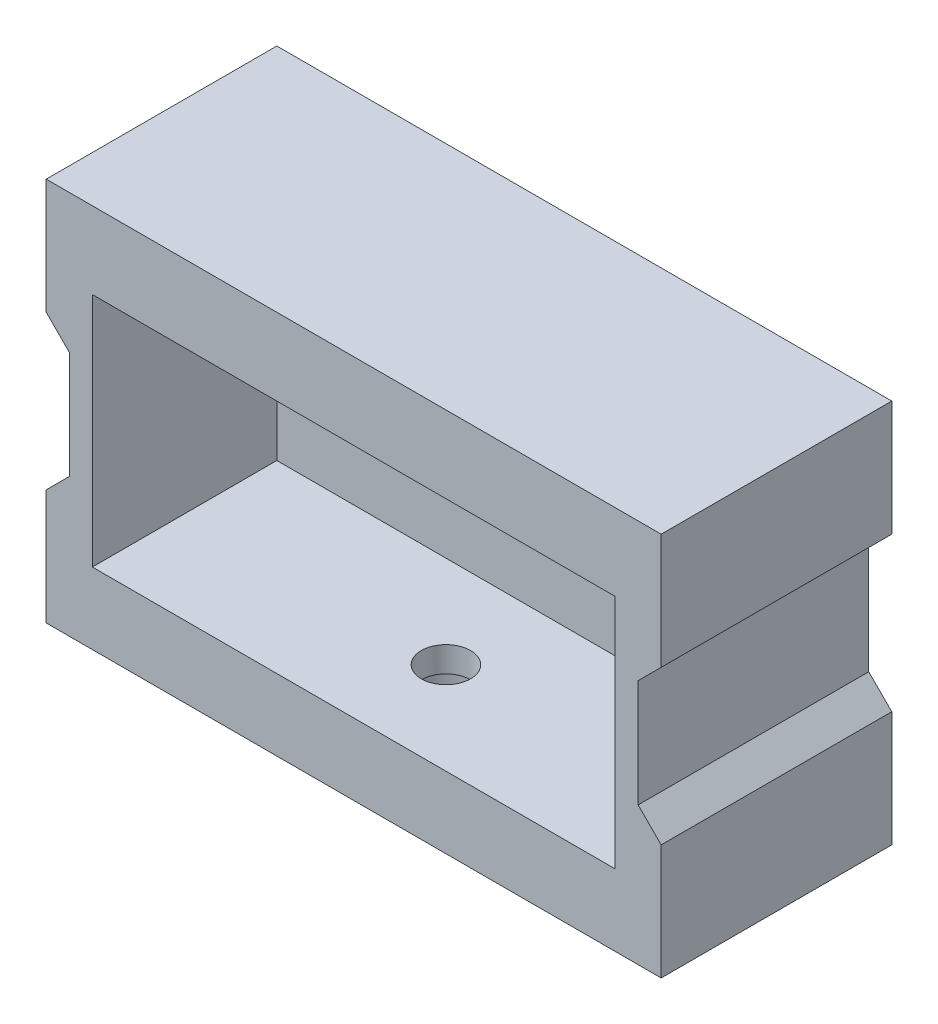
SolidWorks part; units mm, degrees
ref_plane "Płaszczyzna przednia" through (0, 0, 0) normal (0, 0, 1) x (1, 0, 0)
ref_plane "Płaszczyzna górna" through (0, 0, 0) normal (0, 1, 0) x (1, 0, 0)
ref_plane "Płaszczyzna prawa" through (0, 0, 0) normal (1, 0, 0) x (0, 0, -1)
sketch "Sketch1" plane through (0, 0, 0) normal (0, 0, 1) x (1, 0, 0)
  line L1 (-40, -25) -> (40, -25)
  line L2 (-40, -25) -> (-40, 25)
  line L3 (-40, 25) -> (40, 25)
  line L4 (40, -25) -> (40, 25)
  line L5 (-40, -25) -> (40, 25) construction
  line L6 (-40, 25) -> (40, -25) construction
  point P0 (0, 0)
  dimension "D1" = 80
  dimension "D2" = 50
extrude "Boss-Extrude1" add sketch "Sketch1" along normal blind 30
sketch "Sketch2" plane through (0, 0, 0) normal (0, 0, 1) x (1, 0, 0)
  line L0 (-40, 0) -> (40, 0) construction
  line L1 (-40, 25) -> (-40, -25) construction
  line L2 (40, -25) -> (40, 25) construction
  line L4 (-43, -10) -> (-37, -10)
  line L5 (-43, -10) -> (-43, 10)
  line L6 (-43, 10) -> (-37, 10)
  line L7 (-37, -10) -> (-37, 10)
  line L8 (-43, -10) -> (-37, 10) construction
  line L9 (-43, 10) -> (-37, -10) construction
  line L10 (43, -10) -> (37, -10)
  line L11 (43, -10) -> (43, 10)
  line L12 (43, 10) -> (37, 10)
  line L13 (37, -10) -> (37, 10)
  line L14 (43, -10) -> (37, 10) construction
  line L15 (43, 10) -> (37, -10) construction
  dimension "D1" = 10
  dimension "D2" = 10
  dimension "D3" = 3
  dimension "D4" = 3
extrude "Cut-Extrude1" cut sketch "Sketch2" along normal through all both and the other way through all
chamfer "Chamfer1" distance 3 angle 45 4 edges at (37, 10, 15) (37, -10, 15) (-37, -10, 15) (-37, 10, 15)
sketch "Sketch3" plane through (0, 0, 0) normal (0, 0, 1) x (1, 0, 0)
  line L0 (-37, -7) -> (-37, 7) construction
  line L1 (-34, -15) -> (34, -15)
  line L2 (-34, -15) -> (-34, 15)
  line L3 (-34, 15) -> (34, 15)
  line L4 (34, -15) -> (34, 15)
  line L5 (-34, -15) -> (34, 15) construction
  line L6 (-34, 15) -> (34, -15) construction
  line L8 (40, 25) -> (-40, 25) construction
  point P0 (0, 0)
  dimension "D1" = 3
  dimension "D2" = 10
extrude "Cut-Extrude2" cut sketch "Sketch3" against normal blind 24 from surface starting at face at (0, 0, 30)
sketch "Sketch4" plane through (0, 0, 0) normal (0, 1, 0) x (1, 0, 0)
  line L0 (-40, -18) -> (40, -18) construction
  line L3 (0, 0) -> (0, -30) construction
  line L4 (40, -30) -> (-40, -30) construction
  line L5 (40, 0) -> (-40, 0) construction
  circle A0 centre (0, -18) radius 3.2
  dimension "D1" = 6.4
  dimension "D2" = 18
extrude "Cut-Extrude3" cut sketch "Sketch4" against normal through all
sketch "Sketch5" plane through (0, 0, 0) normal (0, 0, 1) x (1, 0, 0)
  line L0 (37, 0) -> (-37, 0) construction
  line L1 (37, 7) -> (37, -7) construction
  line L2 (-37, -7) -> (-37, 7) construction
  line L3 (27, 25) -> (27, -25) construction
  line L4 (40, 25) -> (-40, 25) construction
  line L5 (-40, -25) -> (40, -25) construction
  line L6 (-27, 25) -> (-27, -25) construction
  circle A0 centre (27, 0) radius 1.75
  circle A1 centre (-27, 0) radius 1.75
  dimension "D3" = 3.5
  dimension "D1" = 10
  dimension "D2" = 10
extrude "Cut-Extrude4" cut sketch "Sketch5" along normal through all both and the other way through all
sketch "Sketch6" plane through (0, 0, 0) normal (0, 0, 1) x (1, 0, 0)
  line L1 (-23.5359, 0) -> (-25.2679, 3)
  line L2 (-25.2679, 3) -> (-28.7321, 3)
  line L3 (-28.7321, 3) -> (-30.4641, 0)
  line L4 (-30.4641, 0) -> (-28.7321, -3)
  line L5 (-28.7321, -3) -> (-25.2679, -3)
  line L6 (-25.2679, -3) -> (-23.5359, 0)
  line L7 (30.4641, 0) -> (28.7321, 3)
  line L8 (28.7321, 3) -> (25.2679, 3)
  line L9 (25.2679, 3) -> (23.5359, 0)
  line L10 (23.5359, 0) -> (25.2679, -3)
  line L11 (25.2679, -3) -> (28.7321, -3)
  line L12 (28.7321, -3) -> (30.4641, 0)
  circle A0 centre (-27, 0) radius 3 construction
  circle A1 centre (27, 0) radius 3 construction
  dimension "D1" = 6
  dimension "D2" = 6
extrude "Cut-Extrude5" cut sketch "Sketch6" against normal blind 3 from surface starting at face at (28.75, 0, 6)
sketch "Sketch7" plane through (0, 0, 0) normal (0, 1, 0) x (1, 0, 0)
  circle A0 centre (0, -18) radius 5.25
  dimension "D1" = 10.5
extrude "Cut-Extrude6" cut sketch "Sketch7" along normal blind 6 from surface starting at face at (0, -25, 21.2)
sketch "Sketch10" plane through (0, 0, 0) normal (0, 0, 1) x (1, 0, 0)
  line L0 (34, -15) -> (34, 15) construction
  line L1 (-34, -15) -> (34, -15)
  line L2 (-34, -15) -> (-34, -15.7)
  line L3 (-34, -15.7) -> (34, -15.7)
  line L4 (34, -15) -> (34, -15.7)
  dimension "D1" = 0.7
extrude "Cut-Extrude8" cut sketch "Sketch10" against normal up to surface (-6 mm away) from surface up to face at (27, 0, 6) starting at face at (0, 0, 30)
